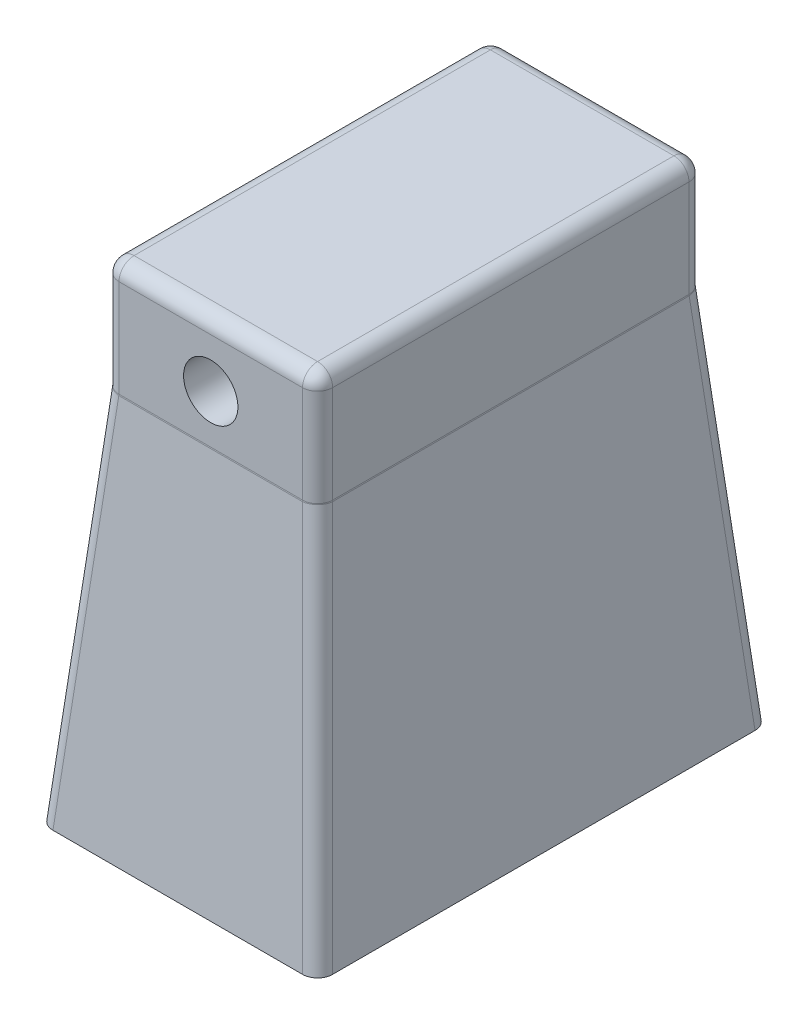
SolidWorks part; units mm, degrees
ref_plane "前视基准面" through (0, 0, 0) normal (0, 0, 1) x (1, 0, 0)
ref_plane "上视基准面" through (0, 0, 0) normal (0, 1, 0) x (1, 0, 0)
ref_plane "右视基准面" through (0, 0, 0) normal (1, 0, 0) x (0, 0, -1)
sketch "草图1" plane through (0, 0, 0) normal (0, 1, 0) x (1, 0, 0)
  line L0 (-185.4, 0) -> (185.4, 0) construction
  line L1 (-185.4, -300) -> (185.4, -300)
  line L2 (-185.4, -300) -> (-185.4, 300)
  line L3 (-185.4, 300) -> (185.4, 300)
  line L4 (185.4, -300) -> (185.4, 300)
  line L5 (-185.4, -300) -> (185.4, 300) construction
  line L6 (-185.4, 300) -> (185.4, -300) construction
  line L7 (0, 300) -> (0, 0) construction
  line L8 (0, 0) -> (0, -300) construction
  circle A4 centre (0, 150) radius 36.025
  circle A5 centre (0, -150) radius 36.025
  point P0 (0, 0)
  point P20 (0, 0)
  dimension "D4" = 72.05
  dimension "D1" = 370.8
  dimension "D2" = 600
extrude "凸台-拉伸1" add sketch "草图1" along normal blind 500 draft 5 contours L2 L1 L4 L3 A4 A5 | A4 | A5 region at (0, 0, 0) region at (0, 0, -150) region at (0, 0, 150)
sketch "草图2" plane through (0, 500, 0) normal (0, 1, 0) x (1, 0, 0)
  line L4 (-141.6557, -256.2557) -> (141.6557, -256.2557)
  line L5 (141.6557, -256.2557) -> (141.6557, 256.2557)
  line L6 (141.6557, 256.2557) -> (-141.6557, 256.2557)
  line L7 (-141.6557, 256.2557) -> (-141.6557, -256.2557)
  line L8 (-141.6557, -256.2557) -> (141.6557, -256.2557)
  line L9 (141.6557, -256.2557) -> (141.6557, 256.2557)
  line L10 (141.6557, 256.2557) -> (-141.6557, 256.2557)
  line L11 (-141.6557, 256.2557) -> (-141.6557, -256.2557)
  dimension "D1" = 0
extrude "凸台-拉伸2" add sketch "草图2" along normal blind 150
sketch "草图3" plane through (0, 0, 256.2557) normal (0, 0, 1) x (1, 0, 0)
  circle A0 centre (0, 565) radius 36.025
  dimension "D2" = 72.05
  dimension "D1" = 565
extrude "切除-拉伸2" cut sketch "草图3" against normal blind 60 contours A0
mirror "镜向1" about plane through (0, 0, 0) normal (0, 0, 1) of "切除-拉伸2"
fillet "圆角2" radius 20 4 edges at (0, 500, 256.2557) (141.6557, 500, 0) (0, 500, -256.2557) (-141.6557, 500, 0)
fillet "圆角3" radius 20 16 edges at (-141.6557, 575.4366, 256.2557) (-141.6747, 500.0008, 256.2747) (-141.6557, 575.4366, -256.2557) (-141.6747, 500.0008, -256.2747) (141.6557, 575.4366, 256.2557) (141.6747, 500.0008, 256.2747) (141.6557, 575.4366, -256.2557) (141.6747, 500.0008, -256.2747) (0, 650, -256.2557) (141.6557, 650, 0) (0, 650, 256.2557) (-141.6557, 650, 0) (-163.5659, 249.5651, 278.1659) (-163.5659, 249.5651, -278.1659) (163.5659, 249.5651, 278.1659) (163.5659, 249.5651, -278.1659)
equation "\"D1@草图1\"=\"D2@草图1\"*0.618"
